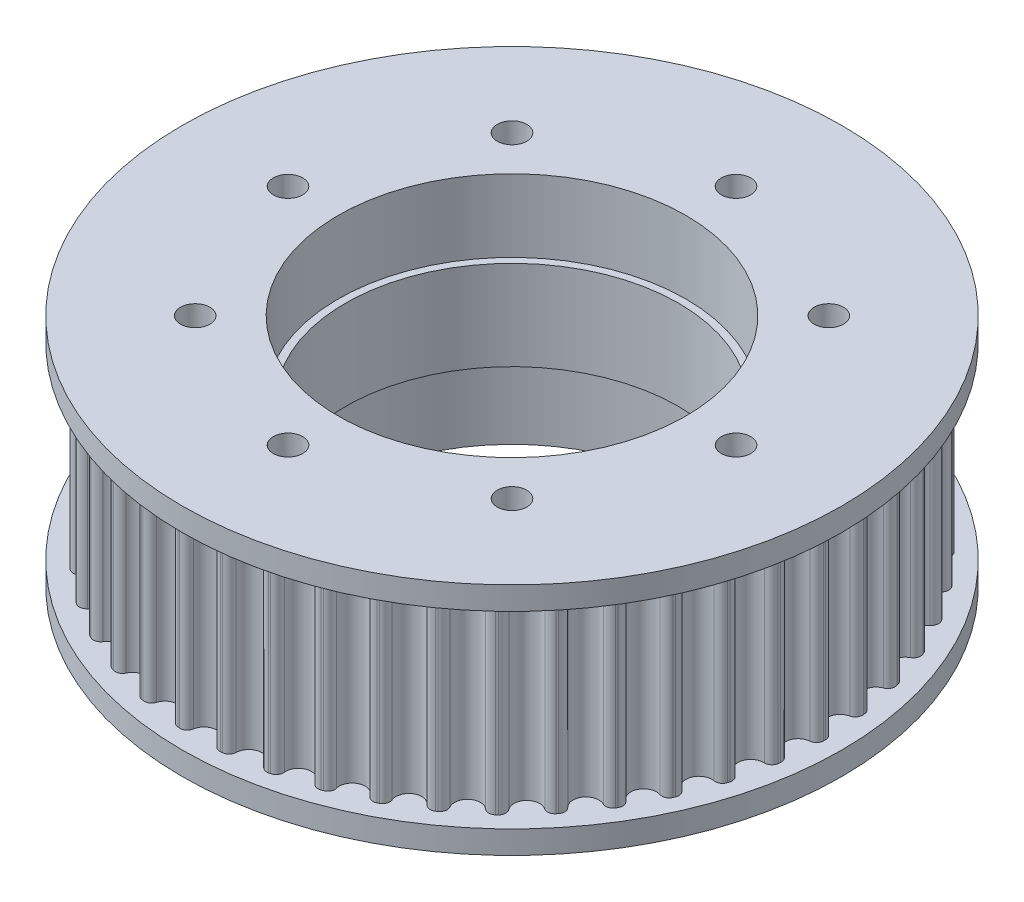
SolidWorks part; units mm, degrees
ref_plane "Front Plane" through (0, 0, 0) normal (0, 0, 1) x (1, 0, 0)
ref_plane "Top Plane" through (0, 0, 0) normal (0, 1, 0) x (1, 0, 0)
ref_plane "Right Plane" through (0, 0, 0) normal (1, 0, 0) x (0, 0, -1)
sketch "Sketch1" plane through (0, 0, 0) normal (0, 1, 0) x (1, 0, 0)
  line L0 (0, 0) -> (0, 21.582) construction
  line L1 (0, 0) -> (2.8938, 21.0541) construction
  circle A0 centre (0, 0) radius 21.582 construction
  circle A1 centre (0, 0) radius 20.362 construction
  circle A2 centre (0, 21.252) radius 0.89 construction
  circle A5 centre (2.8938, 21.0541) radius 0.89 construction
  arc A6 (0, 20.362) -> (0.8793, 21.1145) centre (0, 21.252) ccw
  arc A7 (0.8793, 21.1145) -> (1.4059, 21.5362) centre (1.3733, 21.0373) cw
  arc A8 (1.5397, 21.527) -> (2.004, 21.0376) centre (1.5041, 21.0283) cw
  arc A9 (2.7726, 20.1724) -> (2.004, 21.0376) centre (2.8938, 21.0541) cw
  arc A10 (1.4059, 21.5362) -> (1.5397, 21.527) centre (0, 0) cw
  arc A11 (0, 20.362) -> (2.7726, 20.1724) centre (0, 0) ccw
  dimension "D1" = 43.1641
  dimension "D3" = 1.78
  dimension "D4" = 0.5
  dimension "D2" = 1.22
  dimension "D5" = 7.826
extrude "Boss-Extrude1" add sketch "Sketch1" along normal mid plane 13 contours A6 A11 A9 A8 A7 region at (0.0017, 0, -0.025)
ref_axis "Axis1" through (0, 3.3, 0) along (0, -1, 0)
pattern_circular "CirPattern1" count 46 over 360 about axis through (0, 3.3, 0) along (0, -1, 0) of "Boss-Extrude1"
sketch "Sketch2" plane through (0, 0, 0) normal (1, 0, 0) x (0, 0, -1)
  line L10 (0, 6.5) -> (22.7568, 6.5) construction
  line L11 (0, 6.5) -> (0, 8.0875) construction
  line L12 (0, 8.0875) -> (22.7568, 8.0875) construction
  line L15 (22.7568, 6.5) -> (22.7568, 8.0875) construction
  line L20 (0, 3.3) -> (0, -3.3) construction
  line L22 (22.7568, 8.0875) -> (0, 8.0875)
  line L23 (22.7568, 8.0875) -> (22.7568, 6.5)
  line L24 (22.7568, 6.5) -> (0, 6.5)
  line L25 (0, 8.0875) -> (0, 6.5)
  dimension "D1" = 1.5875
  dimension "D2" = 22.7568
  dimension "D3" = 6.5
revolve "Revolve3" add sketch "Sketch2" angle 360 about axis through (0, 3.3, 0) along (0, -1, 0) region at (0, 7.2937, -11.3784)
mirror "Mirror1" about plane through (0, 0, 0) normal (0, 1, 0) of "Revolve3"
sketch "Sketch3" plane through (0, 0, 0) normal (0, -1, 0) x (-1, 0, 0)
  circle A0 centre (0, 0) radius 11.5
  dimension "D1" = 23
extrude "Cut-Extrude1" cut sketch "Sketch3" against normal through all both and the other way through all
sketch "Sketch5" plane through (0, 0, 0) normal (0, 1, 0) x (1, 0, 0)
  line L0 (-11.5, 0) -> (-19.423, 0) construction
  circle A0 centre (-15.4615, 0) radius 1.016
  circle A1 centre (0, 0) radius 19.423 construction
  circle A2 centre (0, 0) radius 11.5 construction
  dimension "D1" = 2.032
  dimension "D2" = 38.8461
extrude "Cut-Extrude2" cut sketch "Sketch5" against normal through all both and the other way through all
pattern_circular "CirPattern2" count 8 over 360 about axis through (0, 3.3, 0) along (0, -1, 0) of "Cut-Extrude2"
sketch "Sketch8" plane through (0, 0, 0) normal (0, 1, 0) x (1, 0, 0)
  circle A0 centre (0, 0) radius 12
  dimension "D1" = 24
extrude "Cut-Extrude3" cut sketch "Sketch8" along normal blind 5 from surface starting at face at (-1.016, -8.0875, -15.4615)
extrude "Cut-Extrude4" cut sketch "Sketch8<2>" against normal blind 5 from surface starting at face at (-1.016, 8.0875, -15.4615)
sketch "Sketch8<2>" plane through (0, 0, 0) normal (0, 1, 0) x (1, 0, 0) same geometry as "Sketch8"
equation "\"TEETH_NUM\"= 46"
equation "\"TOOTH_PITCH\"= 3mm"
equation "\"PITCH_LINE_OFFSET\"= .015in"
equation "\"DIAMETER_PER_GROOVE\"= \"OUTSIDE_DIAMETER\" / \"TEETH_NUM\" * 1in"
equation "\"PITCH_DIAMETER\"= ( ( \"TEETH_NUM\" * 3 - 1.31 ) / 3.1415 + .415 ) * 1mm"
equation "\"OUTSIDE_DIAMETER\"= \"PITCH_DIAMETER\" - \"PITCH_LINE_OFFSET\" * 2"
equation "\"D1@Sketch1\"=\"OUTSIDE_DIAMETER\""
equation "\"TOOTH_HEIGHT\"= 1.22mm"
equation "\"D2@Sketch1\"=\"TOOTH_HEIGHT\""
equation "\"TOOTH_DIAMETER\"= 1.78mm"
equation "\"INTERNAL_RADIUS\"= .5mm"
equation "\"D3@Sketch1\"=\"TOOTH_DIAMETER\""
equation "\"D5@Sketch1\"=360 / \"TEETH_NUM\""
equation "\"D4@Sketch1\"=\"INTERNAL_RADIUS\""
equation "\"D1@CirPattern1\"=\"TEETH_NUM\""
equation "\"BELT_GAP\"= 13mm"
equation "\"D2@Sketch2\"=\"PITCH_DIAMETER\"/2+1/32"
equation "\"D3@Sketch2\"=\"BELT_GAP\"/2"
equation "\"D1@Sketch3\"=23mm"
equation "\"D1@Boss-Extrude1\"=\"BELT_GAP\""
equation "\"center_offset\"=0.75"
equation "\"Bearing_Diameter\"= 58mm"
equation "\"D2@Sketch5\"=\"PITCH_DIAMETER\"-0.2"
equation "\"Num_Interface_Holes\"= 8"
equation "\"D1@CirPattern2\"=\"Num_Interface_Holes\""
